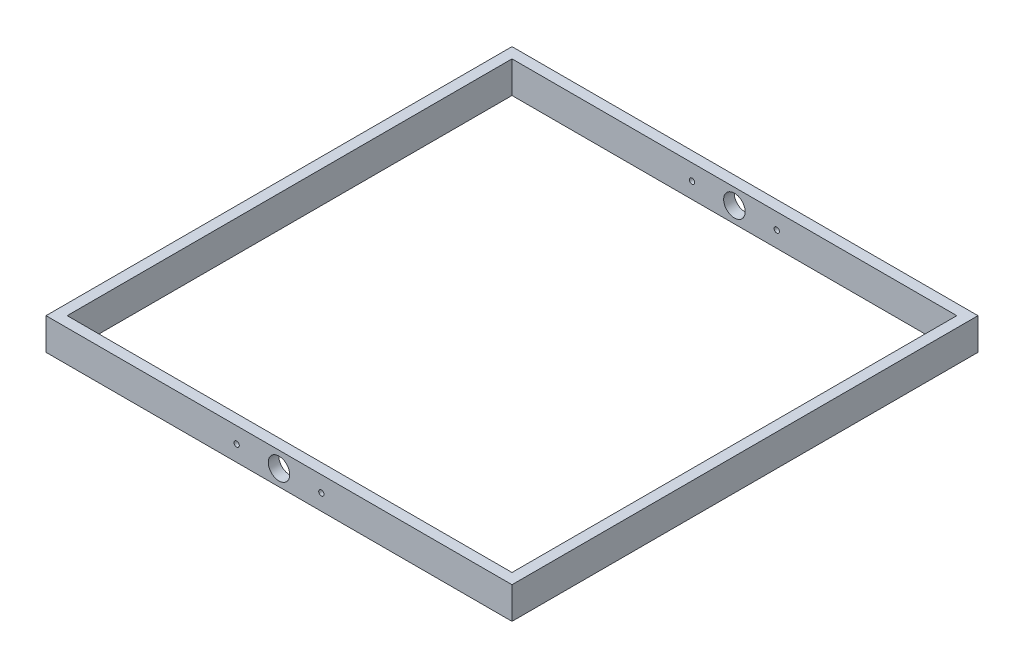
SolidWorks part; units mm, degrees
ref_plane "Front Plane" through (0, 0, 0) normal (0, 0, 1) x (1, 0, 0)
ref_plane "Top Plane" through (0, 0, 0) normal (0, 1, 0) x (1, 0, 0)
ref_plane "Right Plane" through (0, 0, 0) normal (1, 0, 0) x (0, 0, -1)
sketch "Sketch1" plane through (0, 0, 0) normal (0, 1, 0) x (1, 0, 0)
  line L1 (-110, -110) -> (110, -110)
  line L2 (-110, -110) -> (-110, 110)
  line L3 (-110, 110) -> (110, 110)
  line L4 (110, -110) -> (110, 110)
  line L5 (-110, -110) -> (110, 110) construction
  line L6 (-110, 110) -> (110, -110) construction
  point P0 (0, 0)
  dimension "D1" = 220
extrude "Boss-Extrude1" add sketch "Sketch1" along normal blind 15
sketch "Sketch2" plane through (0, 15, 0) normal (0, 1, 0) x (1, 0, 0)
  line L0 (110, 110) -> (-110, 110) construction
  line L1 (-105, -105) -> (105, -105)
  line L2 (-105, -105) -> (-105, 105)
  line L3 (-105, 105) -> (105, 105)
  line L4 (105, -105) -> (105, 105)
  line L5 (-105, -105) -> (105, 105) construction
  line L6 (-105, 105) -> (105, -105) construction
  point P1 (0, 0)
  dimension "D1" = 5
extrude "Cut-Extrude1" cut sketch "Sketch2" against normal blind 15
sketch "Sketch3" plane through (0, 0, 110) normal (0, 0, 1) x (1, 0, 0)
  line L0 (110, 15) -> (110, 0) construction
  circle A0 centre (0, 7.5) radius 5.075
  point P4 (110, 7.5)
  dimension "D1" = 10.15
extrude "Cut-Extrude2" cut sketch "Sketch3" against normal through all
sketch "Sketch4" plane through (0, 0, 110) normal (0, 0, 1) x (1, 0, 0)
  line L0 (-110, 15) -> (-110, 0) construction
  circle A0 centre (-20, 7.5) radius 1.25
  circle A1 centre (20, 7.5) radius 1.25
  circle A2 centre (0, 7.5) radius 5.075 construction
  point P6 (0, 0)
  point P9 (-110, 7.5)
  point P10 (0, 0)
  dimension "D1" = 2.5
  dimension "D2" = 2.5
  dimension "D3" = 20
  dimension "D4" = 40
extrude "Cut-Extrude3" cut sketch "Sketch4" against normal through all
